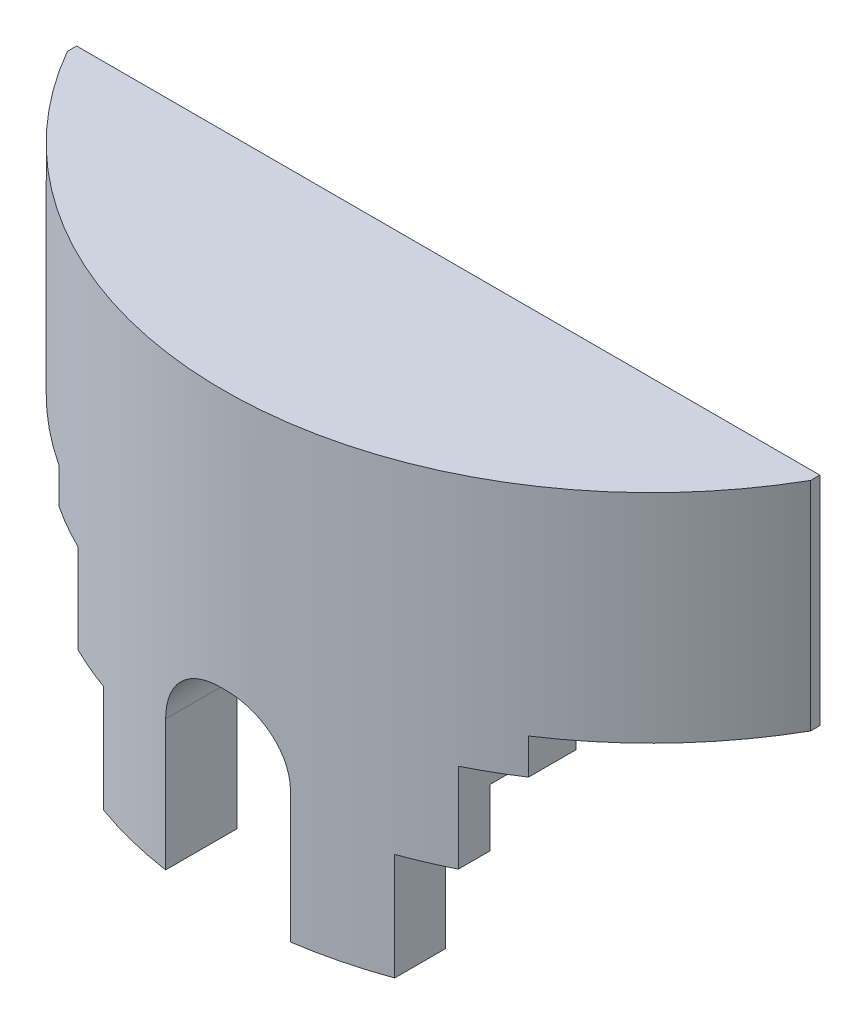
SolidWorks part; units mm, degrees
material "Pure Lead"
ref_plane "Front Plane" through (0, 0, 0) normal (0, 0, 1) x (1, 0, 0)
ref_plane "Top Plane" through (0, 0, 0) normal (0, 1, 0) x (1, 0, 0)
ref_plane "Right Plane" through (0, 0, 0) normal (1, 0, 0) x (0, 0, -1)
sketch "Sketch1" plane through (0, 0, 0) normal (0, 1, 0) x (1, 0, 0)
  line L0 (-62.5, -34.2) -> (-62.5, -35.7456)
  line L1 (-62.5, -34.2) -> (62.5, -34.2)
  line L2 (62.5, -34.2) -> (62.5, -35.7456)
  arc A0 (-62.5, -35.7456) -> (62.5, -35.7456) centre (0, 0) ccw
  dimension "D1" = 144
  dimension "D2" = 125
  dimension "D3" = 34.2
extrude "Boss-Extrude1" add sketch "Sketch1" against normal blind 36.5
sketch "Sketch2" plane through (0, -36.5, 0) normal (0, -1, 0) x (1, 0, 0)
  line L0 (-39.5, 60.1976) -> (-39.5, 34.2)
  line L1 (62.5, 34.2) -> (-62.5, 34.2) construction
  line L2 (-39.5, 34.2) -> (39.5, 34.2)
  line L3 (39.5, 34.2) -> (39.5, 60.1976)
  arc A0 (62.5, 35.7456) -> (-62.5, 35.7456) centre (0, 0) ccw construction
  arc A1 (-39.5, 60.1976) -> (39.5, 60.1976) centre (0, 0) cw
  line M2 (-62.5, 34.2) -> (62.5, 34.2)
  arc M4 (62.5, 35.7456) -> (-62.5, 35.7456) centre (0, 0) ccw
  dimension "D1" = 79
extrude "Boss-Extrude2" add sketch "Sketch2" along normal blind 6 contours L3 L0 M2 M4 region at (0, -36.5, 51.3794)
sketch "Sketch3" plane through (0, -42.5, 0) normal (0, -1, 0) x (1, 0, 0)
  line L0 (-32, 64.4981) -> (-32, 34.2)
  line L1 (-39.5, 34.2) -> (39.5, 34.2) construction
  line L2 (-32, 34.2) -> (32, 34.2)
  line L3 (32, 34.2) -> (32, 64.4981)
  arc A0 (39.5, 60.1976) -> (-39.5, 60.1976) centre (0, 0) ccw construction
  arc A1 (32, 64.4981) -> (-32, 64.4981) centre (0, 0) ccw
  dimension "D1" = 64
extrude "Boss-Extrude3" add sketch "Sketch3" along normal blind 15
sketch "Sketch4" plane through (0, -57.5, 0) normal (0, -1, 0) x (1, 0, 0)
  line L0 (-24.5, 34.2) -> (-24.5, 67.7034)
  line L1 (-32, 34.2) -> (32, 34.2) construction
  line L2 (-24.5, 34.2) -> (24.5, 34.2)
  line L3 (24.5, 34.2) -> (24.5, 67.7034)
  arc A0 (32, 64.4981) -> (-32, 64.4981) centre (0, 0) ccw construction
  arc A1 (-24.5, 67.7034) -> (24.5, 67.7034) centre (0, 0) cw
  dimension "D1" = 49
extrude "Boss-Extrude4" add sketch "Sketch4" along normal blind 18
sketch "Sketch7" plane through (0, 0, 34.2) normal (0, 0, -1) x (-1, 0, 0)
  line L0 (0, -75.5) -> (0, -53.5) construction
  line L1 (24.5, -75.5) -> (-24.5, -75.5) construction
  line L2 (-32.5, -53.5) -> (-32.5, -86)
  line L3 (-32.5, -86) -> (32.5, -86)
  line L4 (32.5, -86) -> (32.5, -53.5)
  arc A0 (32.5, -53.5) -> (-32.5, -53.5) centre (0, -53.5) ccw
  dimension "D2" = 65
  dimension "D1" = 22
extrude "Cut-Extrude2" cut sketch "Sketch7" against normal blind 25
sketch "Sketch5" plane through (0, -75.5, 0) normal (0, -1, 0) x (1, 0, 0)
  line L0 (-24.5, 34.2) -> (24.5, 34.2) construction
  line L1 (-10.5, 34.2) -> (10.5, 34.2)
  line L2 (-10.5, 34.2) -> (-10.5, 72)
  line L3 (-10.5, 72) -> (10.5, 72)
  line L4 (10.5, 34.2) -> (10.5, 72)
  arc A0 (24.5, 67.7034) -> (-24.5, 67.7034) centre (0, 0) ccw construction
  point P6 (0, 72)
  point P10 (0, 72)
  dimension "D1" = 21
extrude "Cut-Extrude1" cut sketch "Sketch5" against normal blind 32
fillet "Fillet1" radius 10 2 edges at (-10.5, -43.5, 65.2151) (10.5, -43.5, 65.2151)
sketch "Sketch8" plane through (0, 0, 34.2) normal (0, 0, -1) x (-1, 0, 0)
  line L0 (-27, -22) -> (27, -22) construction
  line L1 (-27, -2) -> (27, -2)
  line L2 (-27, -42) -> (27, -42)
  line L3 (-62.5, 0) -> (62.5, 0) construction
  arc A0 (-27, -2) -> (-27, -42) centre (-27, -22) ccw
  arc A1 (27, -42) -> (27, -2) centre (27, -22) ccw
  point P2 (0, -22)
  point P7 (-27, -8.0932)
  point P10 (0, 0)
  dimension "D3" = 20
  dimension "D1" = 22
  dimension "D2" = 54
extrude "Cut-Extrude3" cut sketch "Sketch8" against normal blind 18
sketch "Sketch9" plane through (0, 0, 34.2) normal (0, 0, -1) x (-1, 0, 0)
  line L1 (-40.775, -36.5) -> (40.775, -36.5)
  line L2 (-40.775, -36.5) -> (-40.775, -56.5)
  line L3 (-40.775, -56.5) -> (40.775, -56.5)
  line L4 (40.775, -36.5) -> (40.775, -56.5)
  point P4 (-40.775, -36.5)
  point P6 (40.775, -36.5)
  dimension "D1" = 20
extrude "Cut-Extrude4" cut sketch "Sketch9" against normal up to surface (18 mm away) up to face at (0, -27.9799, 52.2)
equation "\"smallPulleyTeeth\"= 30"
equation "\"largePulleyTeeth\"= 30"
equation "\"eighthThick\"= 3.0mm"
equation "\"sixteenthThick\" = 1.7mm"
equation "\"quarterThick\"=6.0mm"
equation "\"OD\" = 145mm"
equation "\"puckAngle\" = 60.5deg"
equation "\"puckDiam\" = 76.5mm"
equation "\"puckDist\" = 85mm"
equation "\"scoopFillet\" = 5mm"
equation "\"axlePress\" = 5.9mm"
equation "\"press\" = 0.2mm"
equation "\"wheelClear\" = 0.3mm"
equation "\"10-32clear\" = 4.8mm"
equation "\"10-32tap\" = 4.45mm"
equation "\"6-32clear\" = 3.3mm"
equation "\"8-32clear\" = 4.0mm"
equation "\"4-40clear\" = 3.0mm"
equation "\"wheelHeight\" = 22mm"
equation "\"wheelWell\" = 65mm"
equation "\"ledSmall\" = 3.1mm"
equation "\"ledLarge\" = 4.2mm"
equation "\"ledLength\" = 4.2mm"
equation "\"4-40close\" = 2.7mm"
equation "\"4-40nutThick\" = 2.2mm"
equation "\"4-40nutWidth\" = 6.2mm"
equation "\"4-40insertHeight\" = 3.5mm"
equation "\"4-40insert\" = 4.25mm"
equation "\"D1@Sketch1\"=\"OD\"-1"
